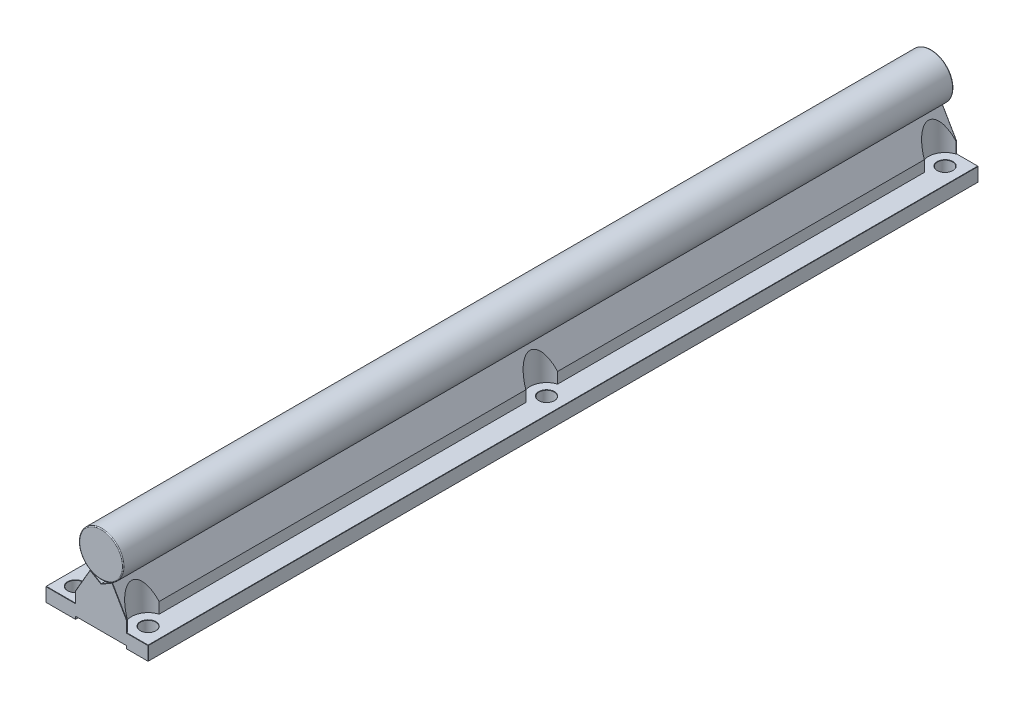
SolidWorks part; units mm, degrees
ref_plane "Front Plane" through (0, 0, 0) normal (0, 0, 1) x (1, 0, 0)
ref_plane "Top Plane" through (0, 0, 0) normal (0, 1, 0) x (1, 0, 0)
ref_plane "Right Plane" through (0, 0, 0) normal (1, 0, 0) x (0, 0, -1)
sketch "Sketch1" plane through (0, 0, 0) normal (0, 0, 1) x (1, 0, 0)
  line L0 (5.8548, 10.2242) -> (5.8548, 5.2242) construction
  line L1 (2.8548, 5.2242) -> (2.8548, 10.2242)
  line L2 (2.8548, 10.2242) -> (13.6048, 10.2242)
  line L3 (13.6048, 14.2028) -> (13.6048, 10.2242)
  line L4 (2.8548, 5.2242) -> (13.6048, 5.2242)
  line L5 (22.8548, 38.4074) -> (22.8548, 3.5658) construction
  line L6 (13.6048, 14.2028) -> (18.8548, 23.296)
  line L8 (39.8548, 10.2242) -> (39.8548, 5.2242)
  line L9 (32.1048, 14.2028) -> (26.8548, 23.296)
  line L10 (32.1048, 14.2028) -> (32.1048, 10.2242)
  line L11 (39.8548, 10.2242) -> (32.1048, 10.2242)
  line L12 (13.6048, 5.2242) -> (13.6048, 6.2242)
  line L13 (13.6048, 6.2242) -> (32.1048, 6.2242)
  line L14 (32.1048, 5.2242) -> (32.1048, 6.2242)
  line L15 (39.8548, 5.2242) -> (32.1048, 5.2242)
  line L16 (18.8548, 23.296) -> (22.8548, 20.9866)
  line L17 (26.8548, 23.296) -> (22.8548, 20.9866)
  circle A0 centre (22.8548, 30.2242) radius 8
  point P4 (2.8548, 10.2242)
  point P15 (22.8548, 4.7443)
  point P23 (22.8548, 6.2242)
  dimension "D5" = 18.5
  dimension "D3" = 16
  dimension "D1" = 1
  dimension "D2" = 8
  dimension "D4" = 20
  dimension "D6" = 25
  dimension "D7" = 37
  dimension "D9" = 60
extrude "Boss-Extrude1" add sketch "Sketch1" against normal blind 300 contours A0
extrude "Boss-Extrude3" add sketch "Sketch1<5>" against normal blind 300 separate body contours L9 L17 L16 L6 L3 L2 L1 L4 L12 L13 L14 L15 L8 L11 L10
sketch "Sketch1<5>" plane through (0, 0, 0) normal (0, 0, 1) x (1, 0, 0) same geometry as "Sketch1"
fillet "Fillet1" radius 0.3 2 edges at (30.8548, 30.2242, -300) (30.8548, 30.2242, 0)
sketch "Sketch2" plane through (0, 10.2242, 0) normal (0, 1, 0) x (1, 0, 0)
  line L0 (39.8548, 300) -> (32.1048, 300) construction
  line L1 (39.8548, 300) -> (39.8548, 0) construction
  line L2 (39.8548, 150) -> (22.8548, 150) construction
  line L3 (22.8548, 300) -> (22.8548, 0) construction
  circle A1 centre (33.8548, 294) radius 6
  dimension "D2" = 12
extrude "Cut-Extrude1" cut sketch "Sketch2" along normal blind 12 contours A1
sketch "Sketch5" plane through (0, 10.2242, 0) normal (0, 1, 0) x (1, 0, 0)
  circle A0 centre (33.8548, 294) radius 2.75
  arc A1 (32.1048, 299.7391) -> (32.1048, 288.2609) centre (33.8548, 294) ccw construction
  dimension "D1" = 5.5
extrude "Cut-Extrude2" cut sketch "Sketch5" against normal blind 5
ref_plane "Plane1" through (0, 0, -150) normal (0, 0, 1) x (1, 0, 0)
mirror "Mirror3" about plane through (0, 0, -150) normal (0, 0, 1) of "Cut-Extrude2", "Cut-Extrude1"
sketch "Sketch9" plane through (0, 10.2242, 0) normal (0, 1, 0) x (1, 0, 0)
  line L0 (2.8548, 300) -> (2.8548, 0) construction
  line L1 (2.8548, 150) -> (39.8548, 150) construction
  line L4 (39.8548, 300) -> (39.8548, 0) construction
  line L6 (2.8548, 300) -> (13.6048, 300) construction
  circle A1 centre (8.2298, 294.62) radius 2.75
  dimension "D1" = 5.375
  dimension "D4" = 5.5
  dimension "D3" = 5.38
extrude "Cut-Extrude3" cut sketch "Sketch9" against normal blind 5
mirror "Mirror5" about plane through (0, 0, -150) normal (0, 0, 1) of "Cut-Extrude3"
pattern_linear "LPattern1" count 2 spacing 144 along (0, 0, 1) of "Cut-Extrude1", "Cut-Extrude2"
sketch "Sketch11" plane through (0, 10.2242, 0) normal (0, 1, 0) x (1, 0, 0)
  point P0 (33.8548, 6)
  point P2 (33.8548, 294)
pattern_linear "LPattern2" count 2 spacing 144 along (0, 0, 1) of "Cut-Extrude3"
chamfer "Chamfer1" distance 0.1 angle 45 28 edges at (2.8548, 7.7242, -300) (39.8548, 7.7242, -300) (35.9798, 10.2242, -300) (32.1048, 12.2135, -300) (29.4798, 18.7494, -300) (24.8548, 22.1413, -300) (20.8548, 22.1413, -300) (16.2298, 18.7494, -300) (13.6048, 12.2135, -300) (8.2298, 10.2242, -300) (2.8548, 7.7242, 0) (39.8548, 7.7242, 0) (39.8548, 10.2242, -150) (35.9798, 10.2242, 0) (32.1048, 12.2135, 0) (29.4798, 18.7494, 0) (24.8548, 22.1413, 0) (20.8548, 22.1413, 0) (16.2298, 18.7494, 0) (13.6048, 12.2135, 0) (8.2298, 10.2242, 0) (2.8548, 10.2242, -150) (31.1048, 10.2242, -6) (5.4798, 10.2242, -5.38) (31.1048, 10.2242, -150) (5.4798, 10.2242, -150.62) (31.1048, 10.2242, -294) (5.4798, 10.2242, -294.62)
